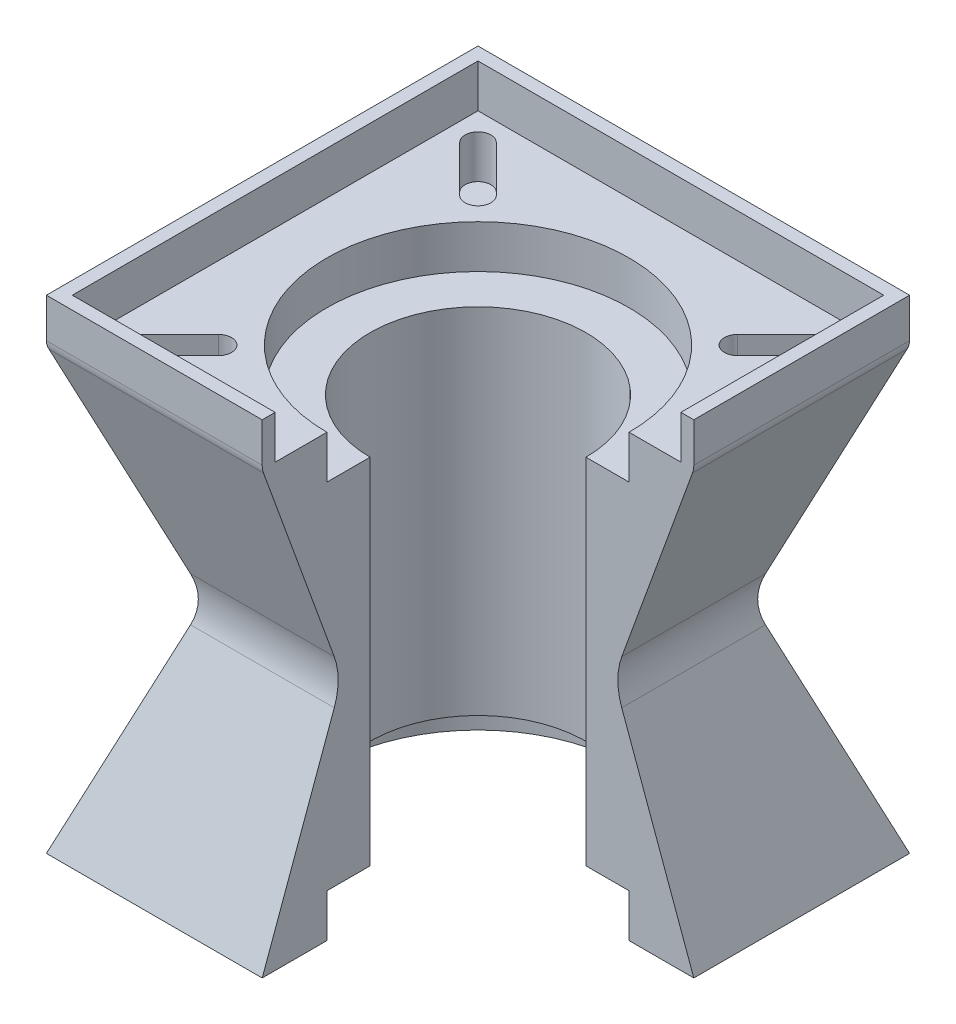
SolidWorks part; units mm, degrees
material "Acier inoxydable moulé"
ref_plane "Plan de face" through (0, 0, 0) normal (0, 0, 1) x (1, 0, 0)
ref_plane "Plan de dessus" through (0, 0, 0) normal (0, 1, 0) x (1, 0, 0)
ref_plane "Plan de droite" through (0, 0, 0) normal (1, 0, 0) x (0, 0, -1)
sketch "Esquisse1" plane through (0, 0, 0) normal (0, 1, 0) x (1, 0, 0)
  line L1 (-50, -50) -> (50, -50)
  line L2 (-50, -50) -> (-50, 50)
  line L3 (-50, 50) -> (50, 50)
  line L4 (50, -50) -> (50, 50)
  line L5 (-50, -50) -> (50, 50) construction
  line L6 (-50, 50) -> (50, -50) construction
  point P0 (0, 0)
  dimension "D1" = 100
  dimension "D2" = 100
ref_plane "Plan de symétrie" through (0, 51, 0) normal (0, 1, 0) x (1, 0, 0)
extrude "Boss.-Extru.1" add sketch "Esquisse1" along normal blind 51 draft 20 contours L1 L4 L3 L2
mirror "Symétrie1" about plane through (0, 51, 0) normal (0, 1, 0) of "Boss.-Extru.1"
sketch "Esquisse3" plane through (0, 102, 0) normal (0, 1, 0) x (1, 0, 0)
  circle A0 centre (0, 0) radius 25
  dimension "D1" = 50
extrude "Enlèv. mat.-Extru.1" cut sketch "Esquisse3" against normal through all
sketch "Esquisse4" plane through (0, 102, 0) normal (0, 1, 0) x (1, 0, 0)
  circle A0 centre (0, 0) radius 35
  dimension "D1" = 70
extrude "Enlèv. mat.-Extru.2" cut sketch "Esquisse4" against normal blind 10
sketch "Esquisse5" plane through (0, 102, 0) normal (0, 1, 0) x (1, 0, 0)
  line L1 (0, 0) -> (50, 0)
  line L2 (0, 0) -> (0, -50)
  line L3 (0, -50) -> (50, -50)
  line L4 (50, 0) -> (50, -50)
extrude "Enlèv. mat.-Extru.3" cut sketch "Esquisse5" against normal through all
mirror "Symétrie2" about plane through (0, 51, 0) normal (0, 1, 0) of "Enlèv. mat.-Extru.2"
fillet "Congé1" radius 15 4 edges at (-31.4375, 51, 0) (0, 51, -31.4375) (31.4375, 51, -15.7188) (-15.7188, 51, 31.4375)
sketch "Esquisse6" plane through (0, 102, 0) normal (0, 1, 0) x (1, 0, 0)
  line L0 (-50, -50) -> (-50, 50) construction
  line L1 (-50, -50) -> (0, -50) construction
  line L6 (50, 0) -> (50, 50) construction
  line L7 (-50, 50) -> (50, 50) construction
  line L8 (-50, -50) -> (-50, 50)
  line L9 (-50, -50) -> (0, -50)
  line L10 (0, -50) -> (0, -47)
  line L11 (0, -35) -> (0, -50) construction
  line L12 (0, -47) -> (-3, -47)
  line L13 (47, 3) -> (47, 0)
  line L14 (50, 0) -> (50, 50)
  line L15 (-50, 50) -> (50, 50)
  line L16 (50, 0) -> (35, 0) construction
  line L17 (47, 0) -> (50, 0)
  line L18 (-47, -47) -> (-3, -47)
  line L19 (-47, -47) -> (-47, 47)
  line L20 (-47, 47) -> (47, 47)
  line L21 (47, 3) -> (47, 47)
  line L24 (35, 3) -> (25, 3) construction
  line L25 (-3, -25) -> (-3, -35) construction
  line L26 (0, -35) -> (0, -50) construction
  line L27 (-3, -35) -> (-3, -47) construction
  line L28 (0, -25) -> (0, -35) construction
  line L29 (50, 0) -> (35, 0) construction
  line L30 (47, 3) -> (35, 3) construction
  line L31 (35, 0) -> (25, 0) construction
  dimension "D1" = 3
extrude "Boss.-Extru.3" add sketch "Esquisse6" along normal blind 10
fillet "Congé2" radius 5 4 edges at (50, 102, -25) (0, 102, -50) (-50, 102, 0) (-25, 102, 50)
sketch "Esquisse7" plane through (0, 102, 0) normal (0, 1, 0) x (1, 0, 0)
  line L0 (0, 0) -> (50, 50) construction
  line L2 (30.052, 30.052) -> (40.6586, 40.6586) construction
  line L3 (27.9307, 32.1734) -> (38.5373, 42.78)
  line L4 (32.1734, 27.9307) -> (42.78, 38.5373)
  arc A0 (27.9307, 32.1734) -> (32.1734, 27.9307) centre (30.052, 30.052) ccw
  arc A1 (42.78, 38.5373) -> (38.5373, 42.78) centre (40.6586, 40.6586) ccw
  point P8 (35.3553, 35.3553)
  point P38 (0, 0)
  dimension "D2" = 3
  dimension "D3" = 50
  dimension "D1" = 15
extrude "Enlèv. mat.-Extru.4" cut sketch "Esquisse7" against normal blind 10
pattern_circular "Répétition circulaire1" count 4 over 360 about axis through (0, 92, 0) along (0, -1, 0) of "Enlèv. mat.-Extru.4"
equation "\"A\"= 102"
equation "\"B\"= 100"
equation "\"C\"= 20"
equation "\"D3@Boss.-Extru.1\"=\"C\""
